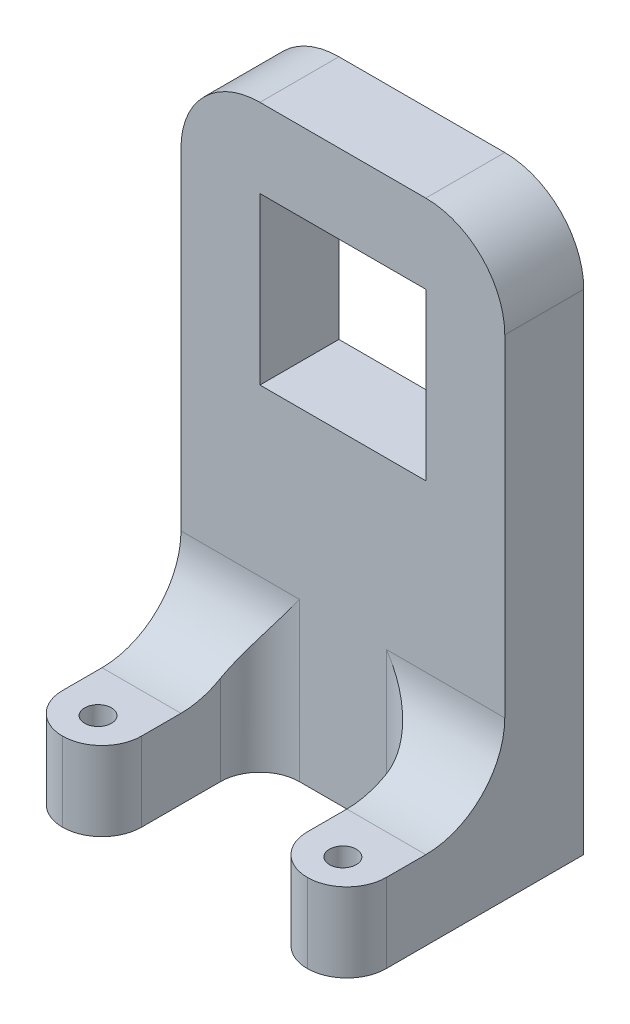
SolidWorks part; units mm, degrees
ref_plane "Plan de face" through (0, 0, 0) normal (0, 0, 1) x (1, 0, 0)
ref_plane "Plan de dessus" through (0, 0, 0) normal (0, 1, 0) x (1, 0, 0)
ref_plane "Plan de droite" through (0, 0, 0) normal (1, 0, 0) x (0, 0, -1)
sketch "Esquisse1" plane through (0, 0, 0) normal (0, 0, 1) x (1, 0, 0)
  line L0 (0, 0) -> (41, 0)
  line L1 (0, 0) -> (41, 0) construction
  line L2 (0, 0) -> (0, 72) construction
  line L3 (0, 72) -> (41, 72) construction
  line L4 (41, 0) -> (41, 72) construction
  line L5 (41, 0) -> (41, 72)
  line L6 (41, 72) -> (0, 72)
  line L7 (0, 72) -> (0, 0)
  line L9 (10, 62) -> (31, 62)
  line L10 (10, 62) -> (10, 41)
  line L11 (10, 41) -> (31, 41)
  line L12 (31, 62) -> (31, 41)
  dimension "D1" = 41
  dimension "D2" = 72
  dimension "D3" = 10
  dimension "D4" = 10
  dimension "D5" = 10
  dimension "D6" = 41
extrude "Boss.-Extru.1" add sketch "Esquisse1" along normal blind 10
sketch "Esquisse3" plane through (0, 0, 10) normal (0, 0, 1) x (1, 0, 0)
  line L0 (31, 0) -> (41, 0)
  line L3 (0, 10) -> (10, 10)
  line L4 (0, 72) -> (0, 0)
  line L5 (0, 0) -> (41, 0)
  line L6 (41, 0) -> (41, 72)
  line L7 (41, 72) -> (0, 72)
  line L8 (0, 10) -> (0, 0)
  line L9 (0, 0) -> (10, 0)
  line L12 (10, 0) -> (10, 10)
  line L14 (41, 0) -> (41, 10)
  line L15 (41, 10) -> (31, 10)
  line L16 (31, 0) -> (31, 10)
  line L17 (0, 0) -> (41, 0) construction
  dimension "D2" = 10
  dimension "D3" = 10
  dimension "D4" = 10
  dimension "D5" = 10
  dimension "D1" = 0
extrude "Boss.-Extru.2" add sketch "Esquisse3" along normal blind 20
sketch "Esquisse4" plane through (0, 10, 0) normal (0, 1, 0) x (1, 0, 0)
  line L0 (0, -30) -> (0, -10) construction
  line L2 (41, -30) -> (41, -10) construction
  line L4 (41, -30) -> (31, -30) construction
  line L5 (10, -30) -> (0, -30) construction
  circle A0 centre (5, -25.5) radius 1.5
  circle A1 centre (36, -25.5) radius 1.5
  dimension "D3" = 3
  dimension "D4" = 3
  dimension "D1" = 5
  dimension "D5" = 5
  dimension "D2" = 4.5
  dimension "D6" = 4.5
hole_wizard "Dégagement M31" positions "Esquisse5" profile "Esquisse6" hole size "M3" standard "ISO" end condition through all
sketch "Esquisse5" plane through (0, 10, 0) normal (0, 1, 0) x (1, 0, 0)
  point P0 (5, -25.5)
  point P3 (36, -25.5)
sketch "Esquisse6" plane through (5, 10, 25.5) normal (1, 0, 0) x (0, 0, 1)
  line L0 (0, 0) -> (0, 10)
  line L1 (0, 10) -> (1.7, 10)
  line L2 (1.7, 10) -> (1.7, 0)
  line L5 (1.7, 0) -> (0, 0)
  line L11 (0, -6.35) -> (0, 107.95) construction
  dimension "Diamètre du perçage jusqu'au prochain" = 3.4
  dimension "Profondeur du perçage jusqu'au prochain" = 10
ref_plane "Plan1" through (0, 0, 5) normal (0, 0, 1) x (1, 0, 0)
fillet "Congé2" radius 10 2 edges at (0, 72, 5) (41, 72, 5)
fillet "Congé3" radius 5 6 edges at (10, 5, 10) (31, 5, 10) (41, 5, 30) (31, 5, 30) (10, 5, 30) (0, 5, 30)
fillet "Congé4" radius 10 2 edges at (33.5, 10, 10) (7.5, 10, 10)
equation "\"largeur_cremail\" = 21"
equation "\"hauteur_cremail\"= 21"
equation "\"epaiss_cadre\"= 10"
equation "\"hauteur_basecremail_sol\"= 122 - 76 - 15"
equation "\"D1@Esquisse1\"=\"largeur_cremail\"+\"epaiss_cadre\"*2"
equation "\"D2@Esquisse1\"=\"hauteur_basecremail_sol\"+\"hauteur_cremail\"+\"epaiss_cadre\"*2"
equation "\"D3@Esquisse1\"=\"epaiss_cadre\""
equation "\"D4@Esquisse1\"=\"epaiss_cadre\""
equation "\"D5@Esquisse1\"=\"epaiss_cadre\""
equation "\"D6@Esquisse1\"=\"hauteur_basecremail_sol\"+\"epaiss_cadre\""
equation "\"D1@Boss.-Extru.1\"=\"epaiss_cadre\""
equation "\"D1@Esquisse4\"=\"epaiss_cadre\"/2"
equation "\"D5@Esquisse4\"=\"epaiss_cadre\"/2"
